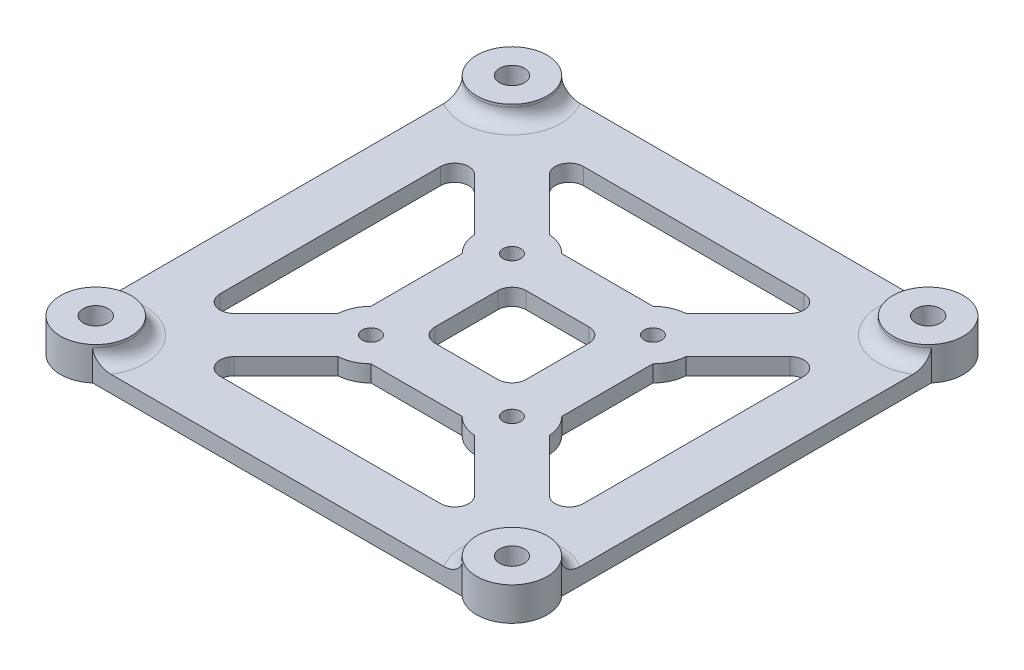
SolidWorks part; units mm, degrees
ref_plane "Front Plane" through (0, 0, 0) normal (0, 0, 1) x (1, 0, 0)
ref_plane "Top Plane" through (0, 0, 0) normal (0, 1, 0) x (1, 0, 0)
ref_plane "Right Plane" through (0, 0, 0) normal (1, 0, 0) x (0, 0, -1)
sketch "Sketch1" plane through (0, 0, 0) normal (0, 1, 0) x (1, 0, 0)
  line L0 (-26.0023, -32.7375) -> (-12.3023, -19.0375)
  line L1 (-12.7, -12.7) -> (12.7, -12.7) construction
  line L2 (-12.7, -12.7) -> (-12.7, 12.7) construction
  line L3 (-12.7, 12.7) -> (12.7, 12.7) construction
  line L4 (12.7, -12.7) -> (12.7, 12.7) construction
  line L5 (-12.7, -12.7) -> (12.7, 12.7) construction
  line L6 (-12.7, 12.7) -> (12.7, -12.7) construction
  line L7 (-37.5, -37.5) -> (37.5, -37.5) construction
  line L8 (-37.5, -37.5) -> (-37.5, 37.5) construction
  line L9 (-37.5, 37.5) -> (37.5, 37.5) construction
  line L10 (37.5, -37.5) -> (37.5, 37.5) construction
  line L11 (-37.5, -37.5) -> (37.5, 37.5) construction
  line L12 (-37.5, 37.5) -> (37.5, -37.5) construction
  line L13 (-33.2999, -42.2625) -> (33.2999, -42.2625)
  line L14 (-33.2999, -42.2625) -> (-33.2999, -32.7375)
  line L15 (-33.2999, -32.7375) -> (33.2999, -32.7375)
  line L16 (33.2999, -42.2625) -> (33.2999, -32.7375)
  line L17 (-33.2999, -42.2625) -> (33.2999, -32.7375) construction
  line L18 (-33.2999, -32.7375) -> (33.2999, -42.2625) construction
  line L19 (32.7375, -33.2999) -> (42.2625, -33.2999)
  line L20 (32.7375, -33.2999) -> (32.7375, 33.2999)
  line L21 (32.7375, 33.2999) -> (42.2625, 33.2999)
  line L22 (42.2625, -33.2999) -> (42.2625, 33.2999)
  line L23 (32.7375, -33.2999) -> (42.2625, 33.2999) construction
  line L24 (32.7375, 33.2999) -> (42.2625, -33.2999) construction
  line L25 (-33.2999, 32.7375) -> (33.2999, 32.7375)
  line L26 (-33.2999, 32.7375) -> (-33.2999, 42.2625)
  line L27 (-33.2999, 42.2625) -> (33.2999, 42.2625)
  line L28 (33.2999, 32.7375) -> (33.2999, 42.2625)
  line L29 (-33.2999, 32.7375) -> (33.2999, 42.2625) construction
  line L30 (-33.2999, 42.2625) -> (33.2999, 32.7375) construction
  line L31 (-42.2625, -33.2999) -> (-32.7375, -33.2999)
  line L32 (-42.2625, -33.2999) -> (-42.2625, 33.2999)
  line L33 (-42.2625, 33.2999) -> (-32.7375, 33.2999)
  line L34 (-32.7375, -33.2999) -> (-32.7375, 33.2999)
  line L35 (-42.2625, -33.2999) -> (-32.7375, 33.2999) construction
  line L36 (-42.2625, 33.2999) -> (-32.7375, -33.2999) construction
  line L41 (-8.2099, -8.2099) -> (8.2099, -8.2099)
  line L42 (-8.2099, -8.2099) -> (-8.2099, 8.2099)
  line L47 (-8.2099, 8.2099) -> (8.2099, 8.2099)
  line L48 (8.2099, -8.2099) -> (8.2099, 8.2099)
  line L53 (-8.2099, -8.2099) -> (8.2099, 8.2099) construction
  line L54 (-8.2099, 8.2099) -> (8.2099, -8.2099) construction
  line L59 (-17.1901, -8.2099) -> (17.1901, -8.2099)
  line L60 (-17.1901, -8.2099) -> (-17.1901, 8.2099)
  line L61 (-17.1901, 8.2099) -> (17.1901, 8.2099)
  line L62 (17.1901, -8.2099) -> (17.1901, 8.2099)
  line L63 (-17.1901, -8.2099) -> (17.1901, 8.2099) construction
  line L64 (-17.1901, 8.2099) -> (17.1901, -8.2099) construction
  line L65 (-8.2099, -17.1901) -> (8.2099, -17.1901)
  line L66 (-8.2099, -17.1901) -> (-8.2099, 17.1901)
  line L67 (-8.2099, 17.1901) -> (8.2099, 17.1901)
  line L68 (8.2099, -17.1901) -> (8.2099, 17.1901)
  line L69 (-8.2099, -17.1901) -> (8.2099, 17.1901) construction
  line L70 (-8.2099, 17.1901) -> (8.2099, -17.1901) construction
  line L71 (-19.0375, -12.3023) -> (-32.7375, -26.0023)
  line L72 (12.3023, -19.0375) -> (26.0023, -32.7375)
  line L73 (19.0375, -12.3023) -> (32.7375, -26.0023)
  line L74 (-12.3023, 19.0375) -> (-26.0023, 32.7375)
  line L75 (-19.0375, 12.3023) -> (-32.7375, 26.0023)
  line L76 (12.3023, 19.0375) -> (26.0023, 32.7375)
  line L77 (19.0375, 12.3023) -> (32.7375, 26.0023)
  circle A4 centre (12.7, 12.7) radius 6.35
  circle A5 centre (12.7, -12.7) radius 6.35
  circle A6 centre (-12.7, -12.7) radius 6.35
  circle A7 centre (-12.7, 12.7) radius 6.35
  circle A8 centre (-37.5, -37.5) radius 6.35
  circle A9 centre (37.5, -37.5) radius 6.35
  circle A10 centre (37.5, 37.5) radius 6.35
  circle A11 centre (-37.5, 37.5) radius 6.35
  point P0 (0, 0)
  point P5 (0, 0)
  point P19 (0, -37.5)
  point P24 (37.5, 0)
  point P29 (0, 37.5)
  point P34 (-37.5, 0)
  point P39 (-12.7, 0)
  point P40 (0, 0)
  point P44 (0, 12.7)
  point P46 (0, 0)
  point P49 (12.7, 0)
  point P52 (0, 0)
  point P53 (0, -12.7)
  dimension "D5" = 12.7
  dimension "D6" = 12.7
  dimension "D7" = 12.7
  dimension "D8" = 12.7
  dimension "D9" = 12.7
  dimension "D10" = 12.7
  dimension "D11" = 12.7
  dimension "D12" = 12.7
  dimension "D2" = 25.4
  dimension "D3" = 75
  dimension "D4" = 75
  dimension "D13" = 9.525
  dimension "D14" = 9.525
  dimension "D15" = 9.525
  dimension "D16" = 9.525
  dimension "D17" = 9.525
  dimension "D18" = 4.7625
  dimension "D19" = 4.7625
  dimension "D20" = 9.525
  dimension "D21" = 4.7625
  dimension "D22" = 9.525
  dimension "D23" = 4.7625
  dimension "D24" = 9.525
extrude "Boss-Extrude1" add sketch "Sketch1" along normal blind 3 contours L31 A8 L14 | L14 A8 L31 | A9 L20 L15 L34 A8 L13 | A6 L71 L34 L15 L0 | A11 L32 A8 L15 L34 L25 | L14 A8 L31 | A6 L66 L59 | A6 L65 A5 L41 | L66 A6 | L59 A6 | A7 L60 A6 L42 | L68 A5 | A5 L59 L68 | L59 A5 | A5 L72 L15 L20 L73 | L16 A9 L19 | L19 A9 L16 | L16 A9 L19 | A9 L15 L20 | L19 A9 L16 | A10 L25 L20 L15 A9 L22 | L31 A8 L14 | A8 L34 L15 | L61 A7 | L66 A7 L61 | L66 A7 | A7 L47 A4 L67 | L68 A4 | L61 A4 L68 | L61 A4 | A5 L62 A4 L48 | A4 L77 L20 L25 L76 | A7 L74 L25 L34 L75 | L28 A10 L21 | L21 A10 L28 | L28 A10 L21 | L21 A10 L28 | A10 L20 L25 | A11 L34 L25 L20 A10 L27 | L33 A11 L26 | L26 A11 L33 | L33 A11 L26 | L26 A11 L33 | A11 L25 L34
sketch "Sketch2" plane through (0, 3, 0) normal (0, 1, 0) x (1, 0, 0)
  circle A0 centre (-37.5, 37.5) radius 6.35
  circle A1 centre (37.5, 37.5) radius 6.35
  circle A2 centre (37.5, -37.5) radius 6.35
  circle A3 centre (-37.5, -37.5) radius 6.35
extrude "Boss-Extrude2" add sketch "Sketch2" along normal blind 3
sketch "Sketch3" plane through (0, 3, 0) normal (0, 1, 0) x (1, 0, 0)
  circle A0 centre (-12.7, 12.7) radius 1.5875
  circle A1 centre (12.7, 12.7) radius 1.5875
  circle A2 centre (12.7, -12.7) radius 1.5875
  circle A3 centre (-12.7, -12.7) radius 1.5875
  dimension "D1" = 3.175
  dimension "D2" = 3.175
  dimension "D3" = 3.175
  dimension "D4" = 3.175
extrude "Cut-Extrude1" cut sketch "Sketch3" against normal through all
fillet "Fillet1" radius 2.54 12 edges at (-8.2099, 1.5, 8.2099) (8.2099, 1.5, 8.2099) (8.2099, 1.5, -8.2099) (-8.2099, 1.5, -8.2099) (-32.7375, 1.5, -26.0023) (-32.7375, 1.5, 26.0023) (-26.0023, 1.5, 32.7375) (26.0023, 1.5, 32.7375) (32.7375, 1.5, 26.0023) (32.7375, 1.5, -26.0023) (26.0023, 1.5, -32.7375) (-26.0023, 1.5, -32.7375)
sketch "Sketch4" plane through (0, 6, 0) normal (0, 1, 0) x (1, 0, 0)
  circle A0 centre (-37.5, 37.5) radius 2.25
  dimension "D1" = 4.5
extrude "Cut-Extrude2" cut sketch "Sketch4" against normal through all
mirror "Mirror1" about plane through (0, 0, 0) normal (1, 0, 0) of "Cut-Extrude2" second plane through (0, 0, 0) second plane normal (0, 0, 1)
fillet "Fillet2" radius 2.54 4 edges at (33.0099, 3, 33.0099) (-33.0099, 3, 33.0099) (-33.0099, 3, -33.0099) (33.0099, 3, -33.0099)
